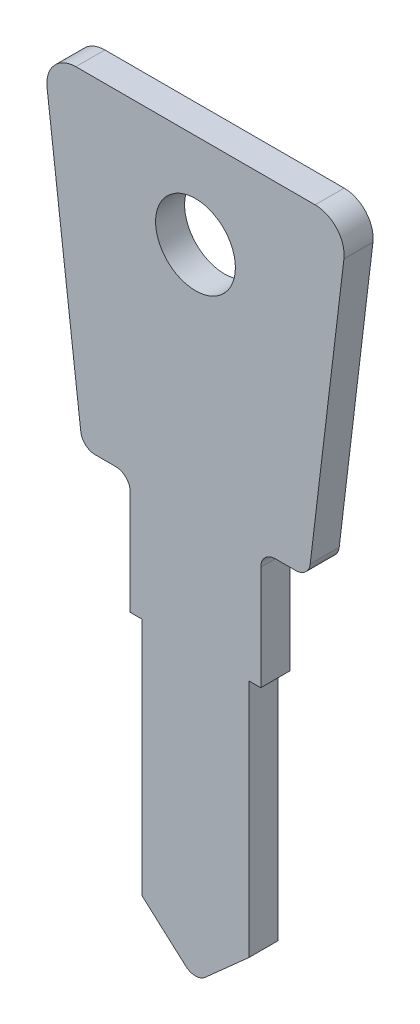
SolidWorks part; units mm, degrees
ref_plane "前视基准面" through (0, 0, 0) normal (0, 0, 1) x (1, 0, 0)
ref_plane "上视基准面" through (0, 0, 0) normal (0, 1, 0) x (1, 0, 0)
ref_plane "右视基准面" through (0, 0, 0) normal (1, 0, 0) x (0, 0, -1)
sketch "草图1" plane through (0, 0, 0) normal (0, 0, 1) x (1, 0, 0)
  line L0 (0, 68.987) -> (0, -54.2213) construction
  line L1 (-56.6306, 0) -> (42.6142, 0) construction
  line L2 (-7.9057, 0.8809) -> (-10.2314, 20.2617)
  line L3 (-8.2457, 22.5) -> (8.2457, 22.5)
  line L4 (-6.9128, 0) -> (-5.5, 0)
  line L5 (-4.5, -1) -> (-4.5, -8.2)
  line L6 (-4.5, -8.2) -> (-3.7, -8.2)
  line L7 (-3.7, -8.2) -> (-3.7, -24.7)
  line L8 (-3.7, -24.7) -> (0, -28)
  line L9 (3.7, -24.7) -> (0, -28)
  line L10 (3.7, -8.2) -> (3.7, -24.7)
  line L11 (4.5, -8.2) -> (3.7, -8.2)
  line L12 (4.5, -1) -> (4.5, -8.2)
  line L13 (6.9128, 0) -> (5.5, 0)
  line L14 (7.9057, 0.8809) -> (10.2314, 20.2617)
  arc A0 (-10.2314, 20.2617) -> (-8.2457, 22.5) centre (-8.2457, 20.5) cw
  arc A1 (-7.9057, 0.8809) -> (-6.9128, 0) centre (-6.9128, 1) ccw
  arc A2 (-5.5, 0) -> (-4.5, -1) centre (-5.5, -1) cw
  arc A3 (5.5, 0) -> (4.5, -1) centre (5.5, -1) ccw
  arc A4 (7.9057, 0.8809) -> (6.9128, 0) centre (6.9128, 1) cw
  arc A5 (10.2314, 20.2617) -> (8.2457, 22.5) centre (8.2457, 20.5) ccw
  point P15 (-10.5, 22.5)
  point P18 (-7.8, 0)
  point P21 (-4.5, 0)
  point P34 (0, 22.5)
  dimension "D9" = 2
  dimension "D10" = 1
  dimension "D11" = 1
  dimension "D1" = 22.5
  dimension "D2" = 10.5
  dimension "D3" = 50.5
  dimension "D4" = 4.5
  dimension "D5" = 8.2
  dimension "D6" = 7.8
  dimension "D7" = 16.5
  dimension "D8" = 3.7
extrude "凸台-拉伸1" add sketch "草图1" along normal blind 1 and the other way blind 1
fillet "圆角1" radius 1 1 edges at (0, -28, 0)
sketch "草图2" plane through (0, 0, 1) normal (0, 0, 1) x (1, 0, 0)
  line L0 (0, 29.7423) -> (0, -37.4968) construction
  line L1 (8.2457, 22.5) -> (-8.2457, 22.5) construction
  circle A0 centre (0, 16) radius 2.75
  dimension "D1" = 5.5
  dimension "D2" = 6.5
extrude "切除-拉伸1" cut sketch "草图2" against normal blind 2
sketch "草图3" plane through (0, 0, -1) normal (0, 0, -1) x (-1, 0, 0)
  line L1 (-4.25, 6.25) -> (4.25, 6.25)
  line L2 (-4.25, 6.25) -> (-4.25, 3)
  line L3 (-4.25, 3) -> (4.25, 3)
  line L4 (4.25, 6.25) -> (4.25, 3)
  point P4 (0, 3)
  dimension "D1" = 8.5
  dimension "D2" = 3.25
  dimension "D3" = 3
extrude "切除-拉伸2" cut sketch "草图3" against normal blind 0.3
sketch "草图4" plane through (0, 0, -0.7) normal (0, 0, -1) x (-1, 0, 0)
  text T0 "2801" font "黑体" height 3
  point P1 (-5, 3)
  point P3 (-5, 3)
  point P4 (-0.3863, 3.3558)
extrude "凸台-拉伸2" add sketch "草图4" along normal blind 0.3
